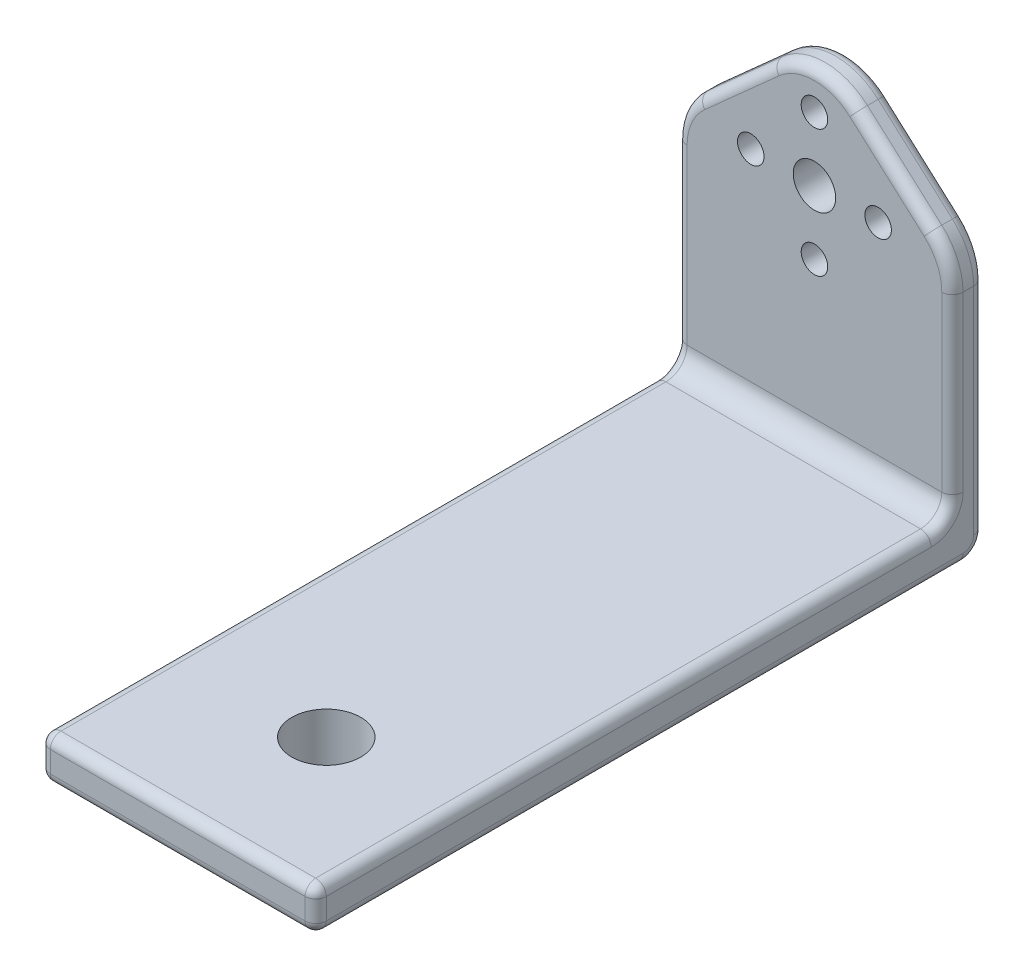
SolidWorks part; units mm, degrees
ref_plane "Front Plane" through (0, 0, 0) normal (0, 0, 1) x (1, 0, 0)
ref_plane "Top Plane" through (0, 0, 0) normal (0, 1, 0) x (1, 0, 0)
ref_plane "Right Plane" through (0, 0, 0) normal (1, 0, 0) x (0, 0, -1)
sketch "Sketch1" plane through (0, 0, 0) normal (0, 0, 1) x (1, 0, 0)
  line L0 (0, 11.4628) -> (0, -12.0557) construction
  line L1 (-13.1568, 0) -> (14.2861, 0) construction
  line L2 (-13, -2.6826) -> (-13, -25)
  line L3 (-11.0009, 1.7888) -> (-4.0009, 8.0523)
  line L4 (13, -2.6826) -> (13, -25)
  line L5 (11.0009, 1.7888) -> (4.0009, 8.0523)
  line L6 (-13, -25) -> (13, -25)
  circle A0 centre (0, 0) radius 2
  circle A1 centre (-6, 0) radius 1.25
  circle A2 centre (0, 6) radius 1.25
  circle A3 centre (6, 0) radius 1.25
  circle A4 centre (0, -6) radius 1.25
  arc A5 (13, -2.6826) -> (11.0009, 1.7888) centre (7, -2.6826) ccw
  arc A6 (4.0009, 8.0523) -> (-4.0009, 8.0523) centre (0, 3.5809) ccw
  arc A7 (-13, -2.6826) -> (-11.0009, 1.7888) centre (-7, -2.6826) cw
  point P18 (0, 0)
  point P23 (13, 0)
  point P26 (0, 11.6322)
  point P29 (-13, 0)
  dimension "D1" = 4
  dimension "D2" = 2.5
  dimension "D6" = 6
  dimension "D3" = 6
  dimension "D5" = 26
  dimension "D7" = 25
  dimension "D4" = 4
extrude "Boss-Extrude1" add sketch "Sketch1" along normal blind 3
sketch "Sketch2" plane through (0, 0, 3) normal (0, 0, 1) x (1, 0, 0)
  line L0 (13, -25) -> (13, -2.6826) construction
  line L1 (-13, -25) -> (13, -25)
  line L2 (-13, -25) -> (-13, -21)
  line L3 (-13, -21) -> (13, -21)
  line L4 (13, -25) -> (13, -21)
  dimension "D1" = 4
extrude "Boss-Extrude2" add sketch "Sketch2" along normal blind 60
sketch "Sketch3" plane through (0, -21, 0) normal (0, 1, 0) x (1, 0, 0)
  line L0 (13, -63) -> (13, -3) construction
  line L2 (13, -3) -> (-13, -3) construction
  circle A0 centre (1, -50) radius 3.25
  point P4 (0, 0)
  point P5 (0, 0)
  dimension "D1" = 6.5
  dimension "D2" = 12
  dimension "D3" = 47
extrude "Cut-Extrude1" cut sketch "Sketch3" against normal through all
sketch "Sketch4" plane through (0, -25, 0) normal (0, -1, 0) x (1, 0, 0)
  line L4 (-13, 0) -> (13, 0)
  line L5 (13, 0) -> (13, 63)
  line L6 (13, 63) -> (-13, 63)
  line L7 (-13, 63) -> (-13, 0)
  line L8 (-13, 0) -> (13, 0)
  line L9 (13, 0) -> (13, 63)
  line L10 (13, 63) -> (-13, 63)
  line L11 (-13, 63) -> (-13, 0)
  circle A0 centre (1, 50) radius 3.25 construction
  circle A1 centre (1, 50) radius 3.25
  circle A2 centre (1, 50) radius 8
  circle M6 centre (1, 50) radius 3.25
  dimension "D2" = 16
  dimension "D1" = 0
extrude "Boss-Extrude3" add sketch "Sketch4" along normal blind 1 contours A2 M6 region at (-6.7737, -25, 50)
sketch "Sketch5" plane through (0, -25, 0) normal (0, -1, 0) x (1, 0, 0)
  line L0 (-13, 10) -> (13, 10) construction
  line L1 (-13, 63) -> (-13, 0) construction
  line L2 (13, 63) -> (13, 0) construction
  line L3 (-13, 0) -> (13, 0) construction
  line L4 (0, 16.476) -> (0, 4.5805) construction
  circle A0 centre (-7.5, 10) radius 1.5
  circle A1 centre (7.5, 10) radius 1.5
  dimension "D2" = 3
  dimension "D1" = 10
  dimension "D3" = 15
extrude "Boss-Extrude4" add sketch "Sketch5" along normal blind 3
fillet "Fillet1" radius 2 2 edges at (0, -21, 3) (0, -25, 0)
fillet "Fillet2" radius 1 26 edges at (13, -21, 34) (13, -20.4142, 3.5858) (13, -10.8413, 3) (12.4775, -0.2336, 3) (7.5009, 4.9205, 3) (0, 9.5809, 3) (-7.5009, 4.9205, 3) (-12.4775, -0.2336, 3) (13, -25, 32.5) (13, -24.4142, 0.5858) (13, -12.8413, 0) (12.4775, -0.2336, 0) (7.5009, 4.9205, 0) (0, 9.5809, 0) (-7.5009, 4.9205, 0) (-12.4775, -0.2336, 0) (-13, -10.8413, 3) (-13, -20.4142, 3.5858) (-13, -21, 34) (-13, -23, 63) (-13, -25, 32.5) (-13, -24.4142, 0.5858) (-13, -12.8413, 0) (0, -21, 63) (13, -23, 63) (0, -25, 63)
fillet "Fillet3" radius 0.5 2 edges at (6, -28, 10) (-6, -28, 10)
